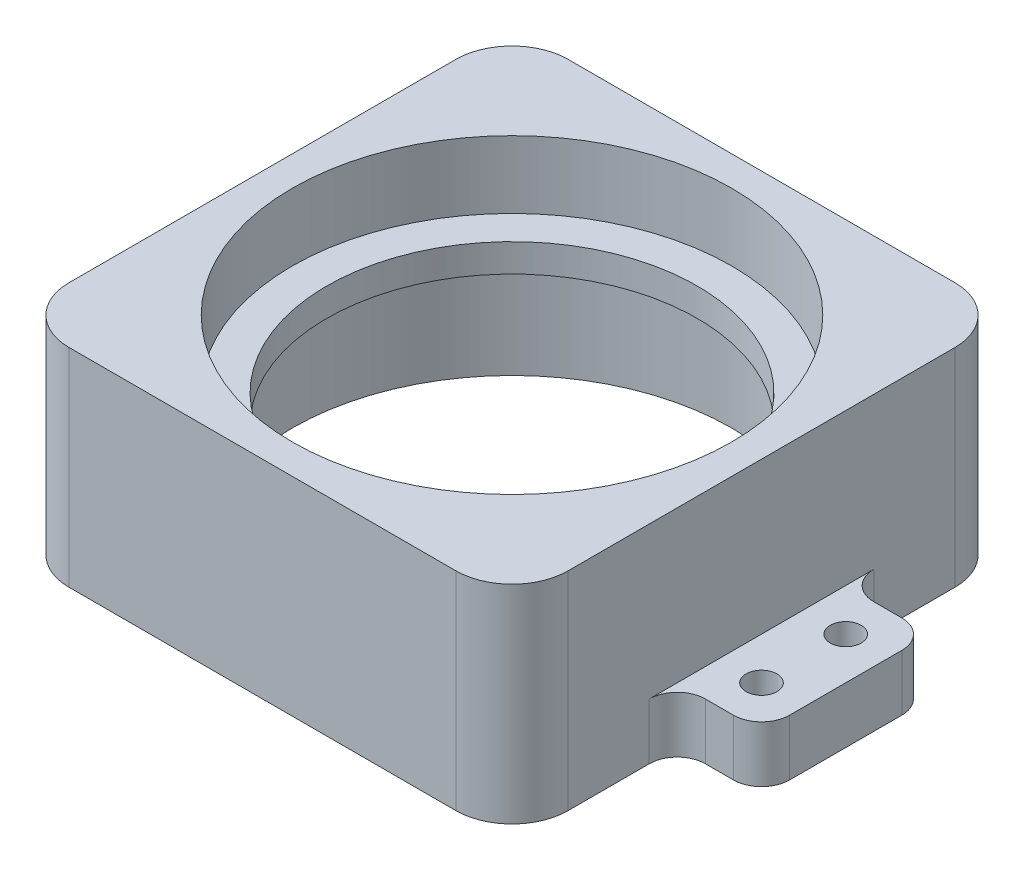
SolidWorks part; units mm, degrees
ref_plane "Front Plane" through (0, 0, 0) normal (0, 0, 1) x (1, 0, 0)
ref_plane "Top Plane" through (0, 0, 0) normal (0, 1, 0) x (1, 0, 0)
ref_plane "Right Plane" through (0, 0, 0) normal (1, 0, 0) x (0, 0, -1)
sketch "Sketch1" plane through (0, 0, 0) normal (0, 1, 0) x (1, 0, 0)
  line L1 (0, 0) -> (88.9, 0)
  line L2 (0, 0) -> (0, 88.9)
  line L3 (0, 88.9) -> (88.9, 88.9)
  line L4 (88.9, 0) -> (88.9, 88.9)
  circle A0 centre (44.45, 44.45) radius 29.88
  circle A1 centre (44.45, 44.45) radius 39.15
  dimension "D1" = 88.9
  dimension "D2" = 88.9
extrude "Boss-Extrude1" add sketch "Sketch1" along normal blind 20 contours L1 L4 L3 L2 A1 region at (1.2572, 0, -44.45)
sketch "Sketch2" plane through (0, 20, 0) normal (0, 1, 0) x (1, 0, 0)
  line L1 (0, 88.9) -> (88.9, 88.9)
  line L2 (0, 88.9) -> (0, 0)
  line L3 (0, 0) -> (88.9, 0)
  line L4 (88.9, 88.9) -> (88.9, 0)
  circle A0 centre (44.45, 44.45) radius 33
extrude "Boss-Extrude3" add sketch "Sketch2" along normal blind 5
sketch "Sketch3" plane through (0, 25, 0) normal (0, 1, 0) x (1, 0, 0)
  line L1 (0, 0) -> (88.9, 0)
  line L2 (0, 0) -> (0, 88.9)
  line L3 (0, 88.9) -> (88.9, 88.9)
  line L4 (88.9, 0) -> (88.9, 88.9)
  circle A0 centre (44.45, 44.45) radius 39.15
extrude "Boss-Extrude4" add sketch "Sketch3" along normal blind 12
sketch "Sketch4" plane through (0, 0, 0) normal (0, -1, 0) x (1, 0, 0)
  line L0 (0, 0) -> (0, -88.9) construction
  line L1 (0, -44.45) -> (-15, -44.45)
  line L2 (0, -44.45) -> (0, -29.45)
  line L3 (0, -29.45) -> (-15, -29.45)
  line L4 (-15, -44.45) -> (-15, -29.45)
  line L5 (88.9, 0) -> (88.9, -88.9) construction
  line L6 (0, -44.45) -> (-15, -44.45)
  line L7 (0, -44.45) -> (0, -59.45)
  line L8 (0, -59.45) -> (-15, -59.45)
  line L9 (-15, -44.45) -> (-15, -59.45)
  line L10 (88.9, -44.45) -> (103.9, -44.45)
  line L11 (88.9, -44.45) -> (88.9, -29.45)
  line L12 (88.9, -29.45) -> (103.9, -29.45)
  line L13 (103.9, -44.45) -> (103.9, -29.45)
  line L15 (88.9, -44.45) -> (103.9, -44.45)
  line L16 (88.9, -44.45) -> (88.9, -59.45)
  line L17 (88.9, -59.45) -> (103.9, -59.45)
  line L18 (103.9, -44.45) -> (103.9, -59.45)
  circle A0 centre (-7.5, -36.95) radius 2.75
  circle A1 centre (-7.5, -51.95) radius 2.75
  circle A2 centre (96.4, -36.95) radius 2.75
  circle A3 centre (96.4, -51.95) radius 2.75
  line M10 (0, 0) -> (0, -88.9)
  line M12 (88.9, -88.9) -> (88.9, 0)
  dimension "D1" = 15
  dimension "D2" = 15
  dimension "D3" = 15
  dimension "D4" = 15
  dimension "D5" = 15
  dimension "D6" = 15
  dimension "D7" = 15
extrude "Boss-Extrude5" add sketch "Sketch4" against normal blind 10 contours L4 L1 L3 A0 M10 | L1 L9 L8 A1 M10 | L10 L13 L12 A2 M12 | L18 L10 L17 A3 M12 region at (-0.2121, 0, -51.95) region at (-7.5, 0, -44.2379) region at (89.1121, 0, -36.95) region at (96.4, 0, -44.6621)
fillet "Fillet1" radius 5 8 edges at (88.9, 5, -59.45) (103.9, 5, -59.45) (103.9, 5, -29.45) (88.9, 5, -29.45) (-15, 5, -59.45) (0, 5, -59.45) (-15, 5, -29.45) (0, 5, -29.45)
fillet "Fillet2" radius 10 4 edges at (0, 18.5, 0) (88.9, 18.5, 0) (88.9, 18.5, -88.9) (0, 18.5, -88.9)
